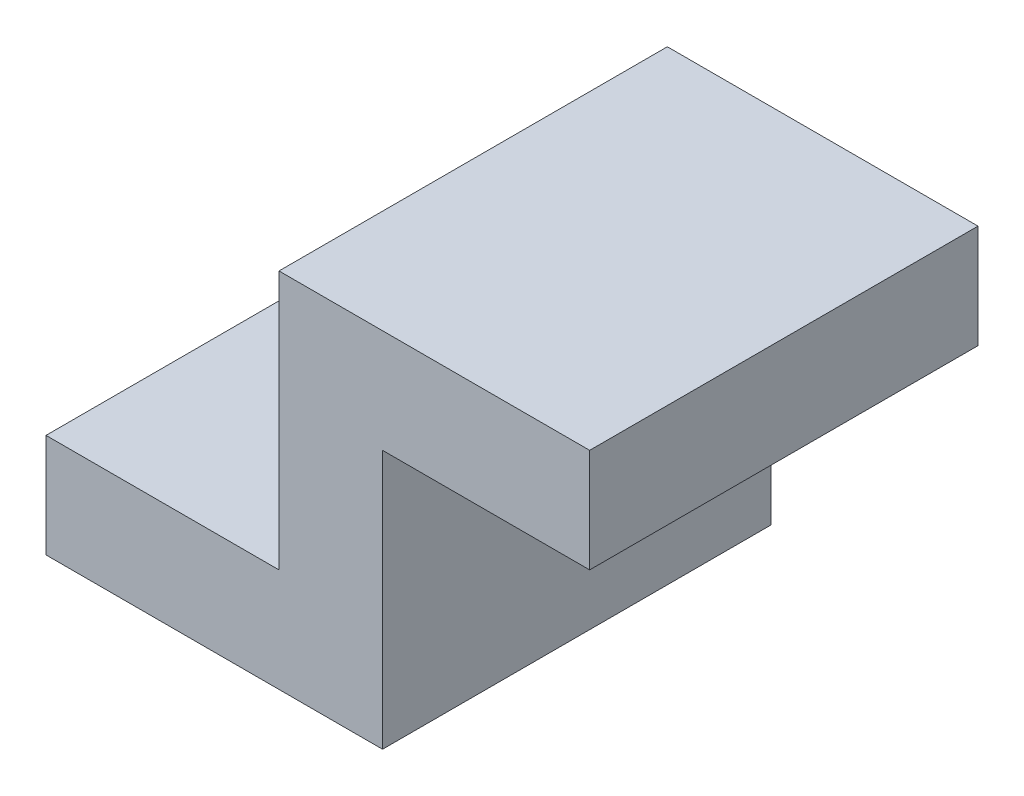
SolidWorks part; units mm, degrees
ref_plane "Front Plane" through (0, 0, 0) normal (0, 0, 1) x (1, 0, 0)
ref_plane "Top Plane" through (0, 0, 0) normal (0, 1, 0) x (1, 0, 0)
ref_plane "Right Plane" through (0, 0, 0) normal (1, 0, 0) x (0, 0, -1)
sketch "Sketch1" plane through (0, 0, 0) normal (0, 0, 1) x (1, 0, 0)
  line L0 (-15.9494, -5.2189) -> (-2.9494, -5.2189)
  line L1 (-2.9494, -5.2189) -> (-2.9494, 4.7811)
  line L2 (-2.9494, 4.7811) -> (5.0506, 4.7811)
  line L3 (5.0506, 4.7811) -> (5.0506, 8.7811)
  line L4 (5.0506, 8.7811) -> (-6.9494, 8.7811)
  line L5 (-6.9494, 8.7811) -> (-6.9494, -1.2189)
  line L6 (-6.9494, -1.2189) -> (-15.9494, -1.2189)
  line L7 (-15.9494, -1.2189) -> (-15.9494, -5.2189)
  dimension "D1" = 10
  dimension "D2" = 4
  dimension "D3" = 8
  dimension "D4" = 4
  dimension "D5" = 4
  dimension "D6" = 9
extrude "Boss-Extrude1" add sketch "Sketch1" along normal blind 15
sketch "Sketch2" plane through (0, -1.2189, 0) normal (0, 1, 0) x (1, 0, 0)
  line L0 (-6.9494, -15) -> (-6.9494, 0) construction
  circle A0 centre (-11.9494, -7.3465) radius 1.5
  dimension "D1" = 3
  dimension "D2" = 5
extrude "Cut-Extrude1" cut sketch "Sketch2" against normal through all
